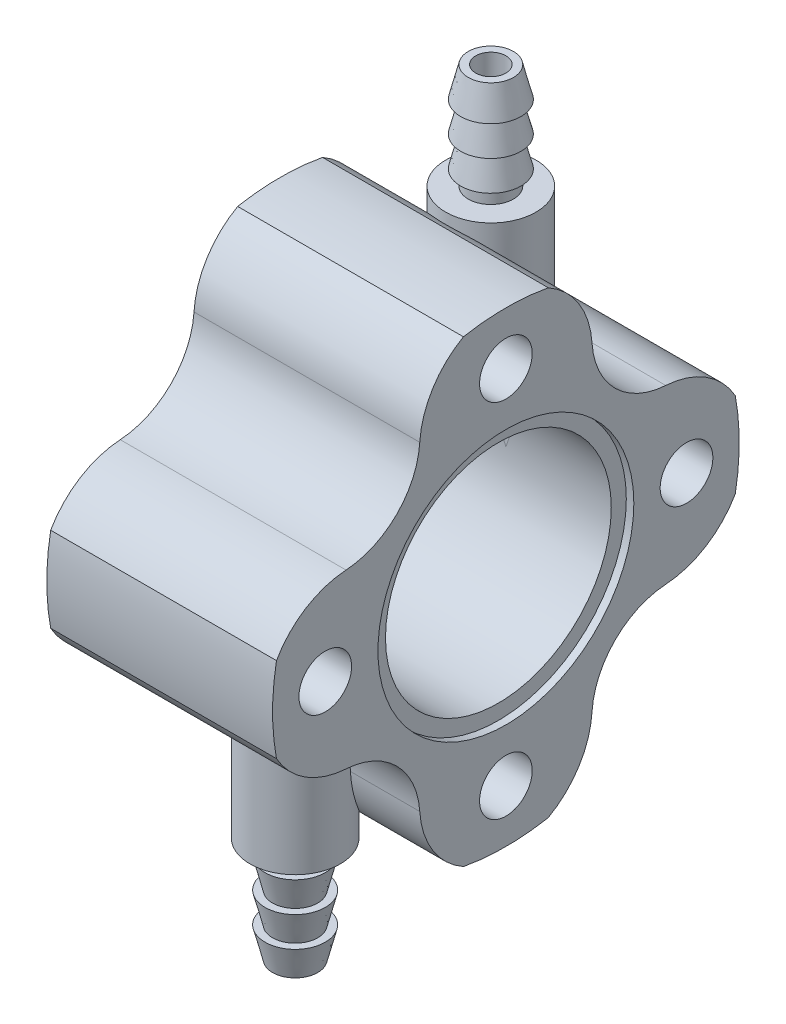
SolidWorks part; units mm, degrees
ref_plane "Front Plane" through (0, 0, 0) normal (0, 0, 1) x (1, 0, 0)
ref_plane "Top Plane" through (0, 0, 0) normal (0, 1, 0) x (1, 0, 0)
ref_plane "Right Plane" through (0, 0, 0) normal (1, 0, 0) x (0, 0, -1)
sketch "Sketch2" plane through (0, 0, 0) normal (1, 0, 0) x (0, 0, -1)
  line L0 (-12, 0) -> (-10.9602, 10.9602) construction
  line L1 (-10.9602, 10.9602) -> (0, 12) construction
  line L2 (0, 55) -> (0, -55) construction
  arc A0 (-15.2412, 2.8209) -> (-15.2412, -2.8209) centre (0, 0) ccw
  circle A1 centre (0, 12) radius 1.75
  circle A2 centre (12, 0) radius 1.75
  circle A3 centre (0, -12) radius 1.75
  circle A4 centre (-12, 0) radius 1.75
  circle A5 centre (0, 0) radius 7.5 construction
  circle A6 centre (0, 0) radius 8.5 construction
  arc A7 (-10.6207, 5.7211) -> (-5.7211, 10.6207) centre (-10.9602, 10.9602) ccw
  circle A8 centre (0, 0) radius 10.25 construction
  arc A9 (-5.7211, 10.6207) -> (-2.8209, 15.2412) centre (0, 10.25) cw
  arc A10 (-2.8209, 15.2412) -> (-6.6728, 13.9901) centre (0, 0) ccw construction
  arc A11 (-5.7336, 11.456) -> (-6.6728, 13.9901) centre (-10.9602, 10.9602) ccw construction
  arc A12 (-6.6728, 13.9901) -> (-10.9602, 10.9602) centre (0, 0) ccw construction
  arc A13 (-10.9602, 10.9602) -> (-13.9901, 6.6728) centre (0, 0) ccw construction
  arc A14 (-5.7211, 10.6207) -> (-5.7336, 11.456) centre (-10.9602, 10.9602) ccw construction
  arc A15 (5.7211, 10.6207) -> (2.8209, 15.2412) centre (0, 10.25) ccw
  arc A16 (5.7211, 10.6207) -> (10.6207, 5.7211) centre (10.9602, 10.9602) ccw
  arc A17 (10.6207, 5.7211) -> (15.2412, 2.8209) centre (10.25, 0) cw
  arc A18 (10.6207, -5.7211) -> (15.2412, -2.8209) centre (10.25, 0) ccw
  arc A19 (10.6207, -5.7211) -> (5.7211, -10.6207) centre (10.9602, -10.9602) ccw
  arc A20 (5.7211, -10.6207) -> (2.8209, -15.2412) centre (0, -10.25) cw
  arc A21 (-5.7211, -10.6207) -> (-2.8209, -15.2412) centre (0, -10.25) ccw
  arc A22 (-5.7211, -10.6207) -> (-10.6207, -5.7211) centre (-10.9602, -10.9602) ccw
  arc A23 (-10.6207, -5.7211) -> (-15.2412, -2.8209) centre (-10.25, 0) cw
  arc A24 (-10.6207, 5.7211) -> (-15.2412, 2.8209) centre (-10.25, 0) ccw
  arc A25 (6.6728, 13.9901) -> (5.7211, 10.6207) centre (10.9602, 10.9602) ccw construction
  arc A26 (13.9901, -6.6728) -> (10.6207, -5.7211) centre (10.9602, -10.9602) ccw construction
  arc A27 (2.8209, -15.2412) -> (13.9901, -6.6728) centre (0, 0) ccw construction
  arc A28 (15.2412, -2.8209) -> (15.2412, 2.8209) centre (0, 0) ccw
  arc A29 (13.9901, -6.6728) -> (15.2412, -2.8209) centre (0, 0) ccw construction
  arc A30 (15.2412, 2.8209) -> (6.6728, 13.9901) centre (0, 0) ccw construction
  arc A31 (2.8209, 15.2412) -> (-2.8209, 15.2412) centre (0, 0) ccw
  arc A32 (-6.6728, -13.9901) -> (-2.8209, -15.2412) centre (0, 0) ccw construction
  arc A33 (-2.8209, -15.2412) -> (2.8209, -15.2412) centre (0, 0) ccw
  arc A34 (-6.6728, -13.9901) -> (-5.7211, -10.6207) centre (-10.9602, -10.9602) ccw construction
  arc A35 (-15.2412, -2.8209) -> (-6.6728, -13.9901) centre (0, 0) ccw construction
  arc A36 (-13.9901, 6.6728) -> (-11.456, 5.7336) centre (-10.9602, 10.9602) ccw construction
  arc A37 (-13.9901, 6.6728) -> (-15.2412, 2.8209) centre (0, 0) ccw construction
  arc A38 (6.6728, 13.9901) -> (2.8209, 15.2412) centre (0, 0) ccw construction
  arc A39 (-11.456, 5.7336) -> (-10.6207, 5.7211) centre (-10.9602, 10.9602) ccw construction
  point P14 (0, 0)
  point P49 (0, 0)
  dimension "D1" = 31
  dimension "D3" = 3.5
  dimension "D5" = 15
  dimension "D6" = 17
  dimension "D7" = 4
  dimension "D4" = 12
  dimension "D2" = 4
extrude "Flange" add sketch "Sketch2" along normal blind 15
sketch "Sketch9" plane through (15, 0, 0) normal (1, 0, 0) x (0, 0, -1)
  circle A0 centre (0, 0) radius 7.5
  dimension "D1" = 15
extrude "Cut-Extrude1" cut sketch "Sketch9" against normal blind 13.5
sketch "Sketch3" plane through (15, 0, 0) normal (1, 0, 0) x (0, 0, -1)
  circle A0 centre (0, 0) radius 8.5
  dimension "D1" = 17
extrude "O-Ring Seat" cut sketch "Sketch3" against normal blind 0.5
ref_plane "MidPlane Reference" through (7.5, 0, 0) normal (-1, 0, 0) x (0, 0, 1)
sketch "Sketch5" plane through (0, 0, 0) normal (0, 1, 0) x (1, 0, 0)
  line L0 (7.5, 15.4) -> (7.5, -15.4) construction
  circle A0 centre (7.5, 6.5) radius 1
  dimension "D1" = 2
  dimension "D2" = 6.5
extrude "Outlet" cut sketch "Sketch5" along normal through all
ref_plane "Plane2" through (0, 15.5, 0) normal (0, 1, 0) x (1, 0, 0)
sketch "Sketch6" plane through (0, 15.5, 0) normal (0, 1, 0) x (1, 0, 0)
  circle A2 centre (7.5, 6.5) radius 1
  circle A3 centre (7.5, 6.5) radius 3
  dimension "D1" = 2
extrude "Boss-Extrude2" add sketch "Sketch6" against normal up to next
sketch "Sketch8" plane through (7.5, 0, 0) normal (-1, 0, 0) x (0, 0, 1)
  line L0 (-8, 15.5) -> (-8, 16.5)
  line L1 (-8, 16.5) -> (-8.5, 16.5)
  line L2 (-8.5, 16.5) -> (-8, 18.5)
  line L3 (-8, 18.5) -> (-8.5, 18.5)
  line L4 (-8.5, 18.5) -> (-8, 20.5)
  line L5 (-8, 20.5) -> (-8.5, 20.5)
  line L6 (-8.5, 20.5) -> (-8, 22.5)
  line L7 (-8, 22.5) -> (-7.5, 22.5)
  line L8 (-7.5, 22.5) -> (-7.5, 15.5)
  line L9 (-7.5, 15.5) -> (-8, 15.5)
  line L10 (-3.5, 15.5) -> (-9.5, 15.5) construction
  line L11 (-5.5, 15.5) -> (-7.5, 15.5) construction
  point P14 (-6.5, 15.5)
  dimension "D1" = 1
  dimension "D2" = 0.5
  dimension "D3" = 0.5
  dimension "D4" = 2
  dimension "D5" = 1
ref_axis "Axis1" through (7.5, 15.5, -6.5) along (0, -1, 0)
revolve "Revolve1" add sketch "Sketch8" angle 360 about axis through (7.5, 15.5, -6.5) along (0, -1, 0)
pattern_circular "CirPattern1" count 2 every 180 about axis through (1.5, 0, 0) along (1, 0, 0) of "Outlet", "Boss-Extrude2", "Revolve1" reverse direction yes
sketch "Sketch10" plane through (1.5, 0, 0) normal (1, 0, 0) x (0, 0, -1)
  line L0 (-5.3033, -5.3033) -> (5.3033, 5.3033) construction
  line L1 (-5.3033, -5.3033) -> (5.3033, -5.3033)
  line L2 (-5.3033, -5.3033) -> (-5.3033, 5.3033)
  line L3 (-5.3033, 5.3033) -> (5.3033, 5.3033)
  line L4 (5.3033, -5.3033) -> (5.3033, 5.3033)
  circle A0 centre (0, 0) radius 7.5 construction
  dimension "D1" = 15
extrude "Cut-Extrude2" cut sketch "Sketch10" against normal blind 0.5
sketch "Sketch12" plane through (1, 0, 0) normal (1, 0, 0) x (0, 0, -1)
  line L0 (-4.8033, -4.8033) -> (4.8033, 4.8033) construction
  line L1 (5.3033, -5.3033) -> (5.3033, 5.3033) construction
  line L2 (-5.3033, -5.3033) -> (5.3033, -5.3033) construction
  circle A0 centre (4.8033, 4.8033) radius 0.5
  circle A1 centre (-4.8033, -4.8033) radius 0.5
  dimension "D1" = 1
extrude "Cut-Extrude3" cut sketch "Sketch12" against normal through all
chamfer "Chamfer1" distance 1 angle 45 2 edges at (0, -4.8033, 4.3033) (0, 4.8033, -5.3033)
